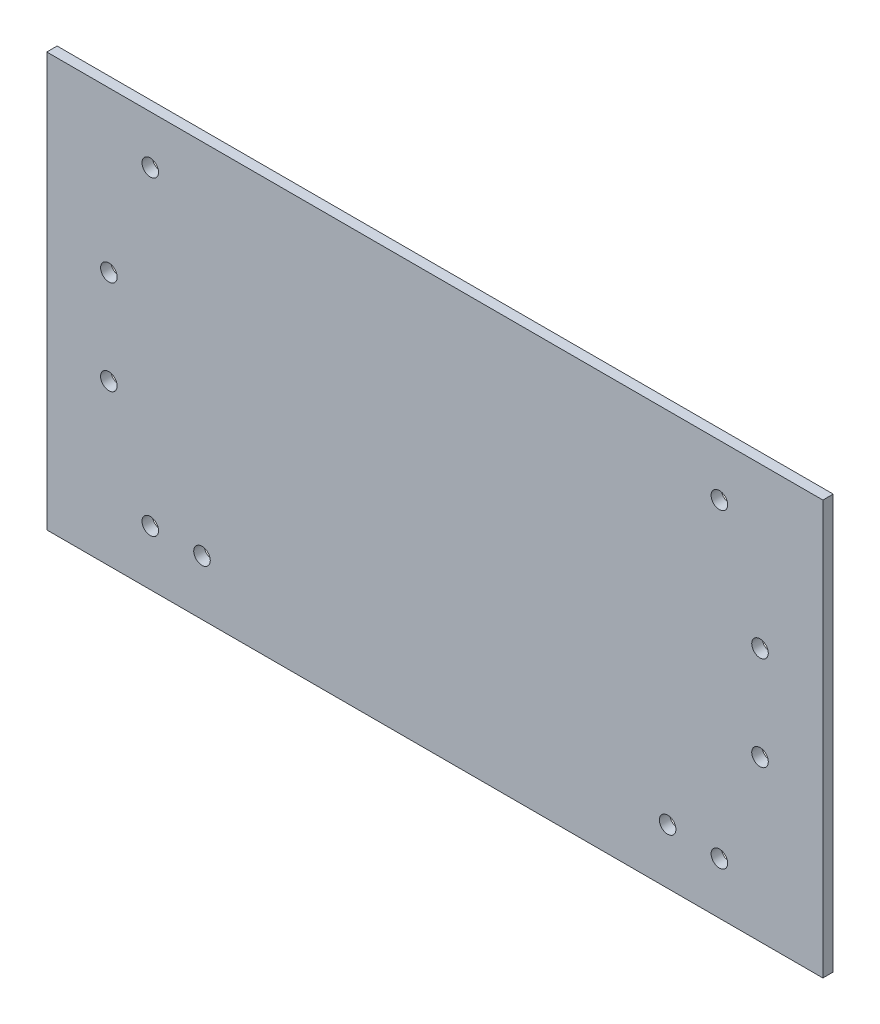
SolidWorks part; units mm, degrees
ref_plane "Front Plane" through (0, 0, 0) normal (0, 0, 1) x (1, 0, 0)
ref_plane "Top Plane" through (0, 0, 0) normal (0, 1, 0) x (1, 0, 0)
ref_plane "Right Plane" through (0, 0, 0) normal (1, 0, 0) x (0, 0, -1)
sketch "Sketch1" plane through (0, 0, 0) normal (0, 0, 1) x (1, 0, 0)
  line L0 (-75, 0) -> (-63, 0) construction
  line L1 (-75, -40) -> (75, -40)
  line L2 (-75, -40) -> (-75, 40)
  line L3 (-75, 40) -> (75, 40)
  line L4 (75, -40) -> (75, 40)
  line L5 (75, 0) -> (62.85, 0) construction
  line L6 (-63, 0) -> (-63, 9.1) construction
  line L7 (-63, 0) -> (-63, -9.1) construction
  line L8 (62.85, 0) -> (62.85, -9.1) construction
  line L9 (62.85, 0) -> (62.85, 9.1) construction
  line L10 (-75, 40) -> (75, -40) construction
  line L11 (-75, -40) -> (75, 40) construction
  line L12 (75, 40) -> (75, 30) construction
  line L13 (40, 40) -> (-40, 40)
  line L14 (40, 40) -> (40, -40)
  line L15 (40, -40) -> (-40, -40)
  line L16 (-40, 40) -> (-40, -40)
  line L17 (0, -40) -> (0, 40) construction
  line L18 (40, 0) -> (-40, 0) construction
  line L19 (75, 30) -> (55, 30) construction
  line L20 (55, 30) -> (55, -30) construction
  line L21 (-75, 40) -> (-75, 30.6667) construction
  line L22 (-75, 30.6667) -> (-55, 30.6667) construction
  line L23 (-55, 30.6667) -> (-55, -29.3333) construction
  circle A0 centre (-63, 9.1) radius 1.6
  circle A1 centre (-63, -9.1) radius 1.6
  circle A2 centre (62.85, 9.1) radius 1.6
  circle A3 centre (62.85, -9.1) radius 1.6
  circle A4 centre (55, 30) radius 1.6
  circle A5 centre (55, -30) radius 1.6
  circle A6 centre (-55, -29.3333) radius 1.6
  circle A7 centre (-55, 30.6667) radius 1.6
  circle A8 centre (-45, -29.3333) radius 1.6
  circle A9 centre (45, -29.3333) radius 1.6
  point P0 (0, 0)
  point P16 (0, 0)
  point P34 (0, -29.3333)
  dimension "D3" = 12
  dimension "D6" = 18.2
  dimension "D7" = 110
  dimension "D9" = 90
  dimension "D1" = 150
  dimension "D2" = 80
  dimension "D4" = 12.15
  dimension "D5" = 10
  dimension "D8" = 60
extrude "Boss-Extrude1" add sketch "Sketch1" along normal blind 2 contours L3 L14 L1 L4 A5 A4 A3 A2 | L3 L16 L1 L14 | L16 L3 L2 L1 A7 A6 A1 A0 region at (-57.5189, 0.0816, 0) region at (0, 0, 0) region at (57.5198, 0.0855, 0)
